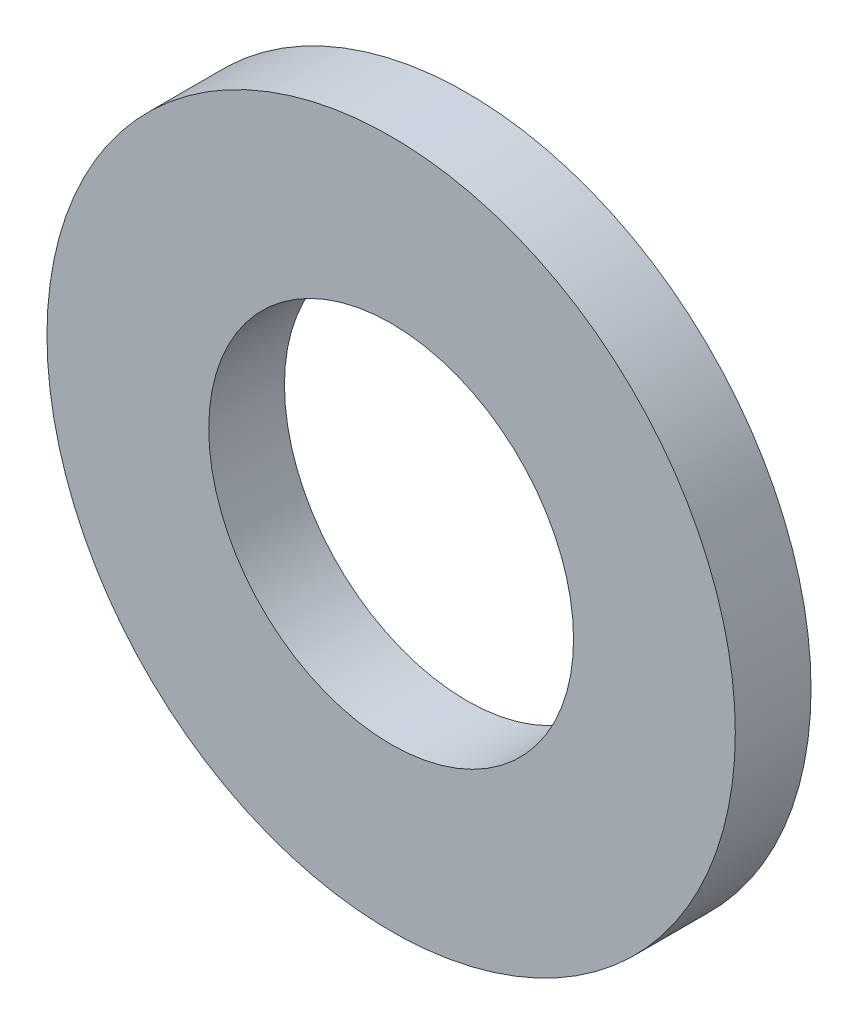
SolidWorks part; units mm, degrees
material "Brass"
ref_plane "Front Plane" through (0, 0, 0) normal (0, 0, 1) x (1, 0, 0)
ref_plane "Top Plane" through (0, 0, 0) normal (0, 1, 0) x (1, 0, 0)
ref_plane "Right Plane" through (0, 0, 0) normal (1, 0, 0) x (0, 0, -1)
sketch "Sketch1" plane through (0, 0, 0) normal (0, 0, 1) x (1, 0, 0)
  circle A0 centre (0, 0) radius 5
  circle A1 centre (0, 0) radius 2.65
  dimension "OD" = 10
  dimension "ID1" = 5.3
extrude "Boss-Extrude1" add sketch "Sketch1" along normal blind 1.1
ref_axis "Axis1" through (0, 0, -0.055) along (0, 0, 1)
